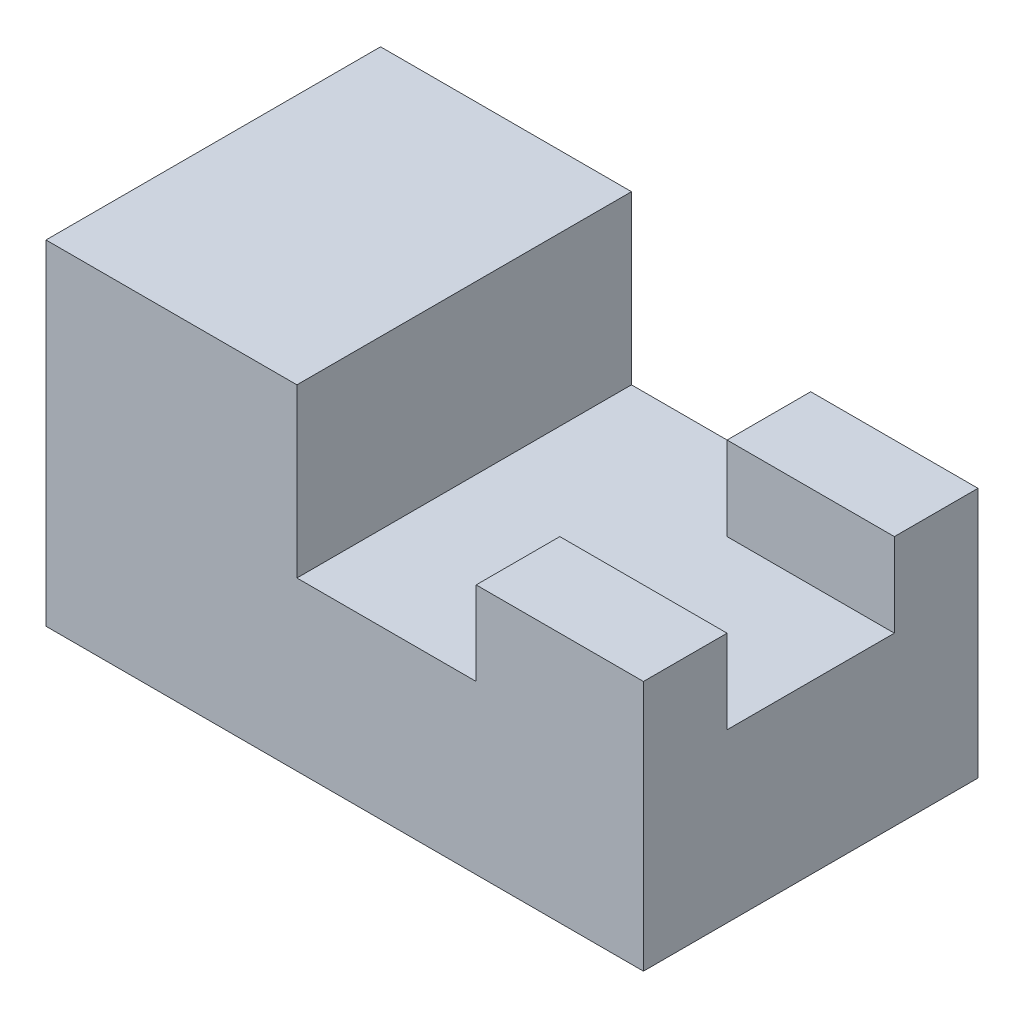
SolidWorks part; units mm, degrees
ref_plane "Front Plane" through (0, 0, 0) normal (0, 0, 1) x (1, 0, 0)
ref_plane "Top Plane" through (0, 0, 0) normal (0, 1, 0) x (1, 0, 0)
ref_plane "Right Plane" through (0, 0, 0) normal (1, 0, 0) x (0, 0, -1)
sketch "Sketch1" plane through (0, 0, 0) normal (0, 1, 0) x (1, 0, 0)
  line L0 (-4, 14) -> (-4, -14)
  line L1 (-25, 14) -> (25, 14)
  line L2 (-25, 14) -> (-25, -14)
  line L3 (-25, -14) -> (25, -14)
  line L4 (25, 14) -> (25, -14)
  line L5 (-25, 14) -> (25, -14) construction
  line L6 (-25, -14) -> (25, 14) construction
  line L8 (25, 14) -> (11, 14)
  line L9 (25, 14) -> (25, 7)
  line L10 (25, 7) -> (11, 7)
  line L11 (11, 14) -> (11, 7)
  line L12 (25, -7) -> (11, -7)
  line L13 (25, -7) -> (25, -14)
  line L14 (25, -14) -> (11, -14)
  line L15 (11, -7) -> (11, -14)
  point P0 (0, 0)
  dimension "D1" = 28
  dimension "D2" = 50
  dimension "D3" = 14
  dimension "D4" = 21
  dimension "D5" = 7
extrude "Boss-Extrude1" add sketch "Sketch1" along normal blind 14 contours L15 L12 L4 L10 L11 L1 L0 L3 region at (8.1136, 0, 0)
extrude "Boss-Extrude2" add sketch "Sketch1<3>" along normal blind 28 contours L2 L3 L0 L1 region at (-14.5, 0, 0)
sketch "Sketch1<3>" plane through (0, 0, 0) normal (0, 1, 0) x (1, 0, 0) same geometry as "Sketch1"
extrude "Boss-Extrude3" add sketch "Sketch1<4>" along normal blind 21 contours L12 L15 L3 L4 | L1 L11 L10 L4 region at (18, 0, -10.5) region at (18, 0, 10.5)
sketch "Sketch1<4>" plane through (0, 0, 0) normal (0, 1, 0) x (1, 0, 0) same geometry as "Sketch1"
